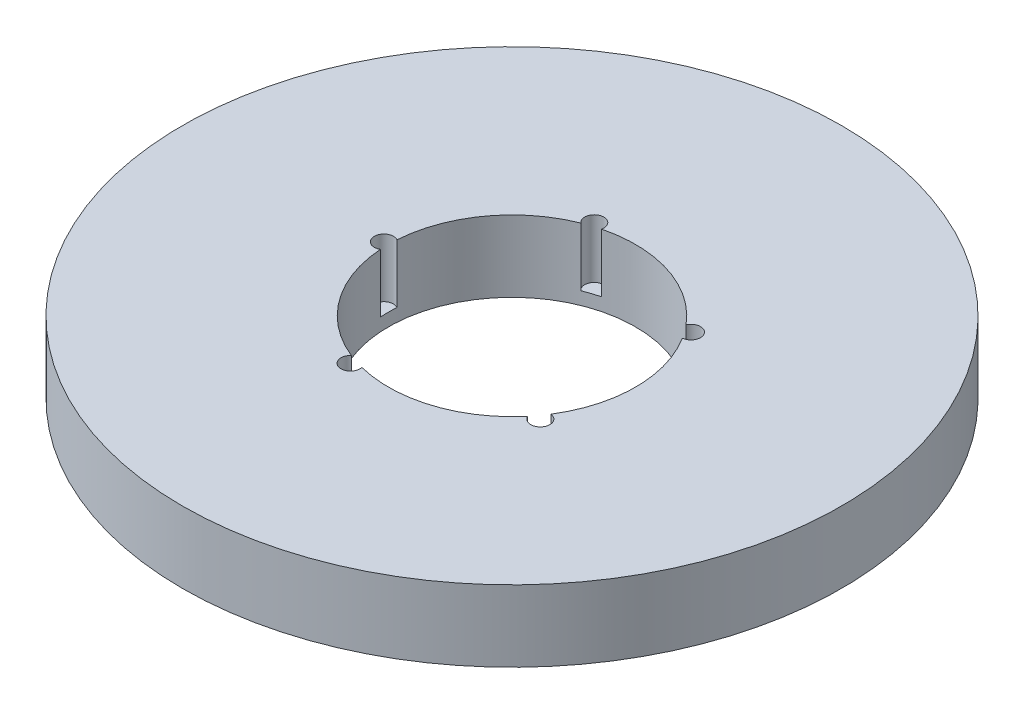
SolidWorks part; units mm, degrees
ref_plane "Front Plane" through (0, 0, 0) normal (0, 0, 1) x (1, 0, 0)
ref_plane "Top Plane" through (0, 0, 0) normal (0, 1, 0) x (1, 0, 0)
ref_plane "Right Plane" through (0, 0, 0) normal (1, 0, 0) x (0, 0, -1)
sketch "Sketch1" plane through (0, 0, 0) normal (0, 1, 0) x (1, 0, 0)
  circle A0 centre (0, 0) radius 60
  dimension "FLANGE_OD" = 120
extrude "Boss-Extrude1" add sketch "Sketch1" along normal blind 13
sketch "Sketch2" plane through (0, 0, 0) normal (0, 1, 0) x (1, 0, 0)
  circle A0 centre (0, 0) radius 22.5
  dimension "BORE_D" = 45
extrude "Cut-Extrude1" cut sketch "Sketch2" along normal through all
sketch "Sketch3" plane through (0, 13, 0) normal (0, 1, 0) x (1, 0, 0)
  circle A0 centre (0, 0) radius 23.3288 construction
  circle A1 centre (-23.3288, 0) radius 1.7425
  dimension "BOLT_D" = 3.4851
  dimension "BOLT_PCD" = 46.6576
extrude "Cut-Extrude2" cut sketch "Sketch3" against normal blind 10.6755
pattern_circular "CirPattern1" count 5 over 360 about axis through (0, 0, 0) along (0, 1, 0) of "Cut-Extrude2"
